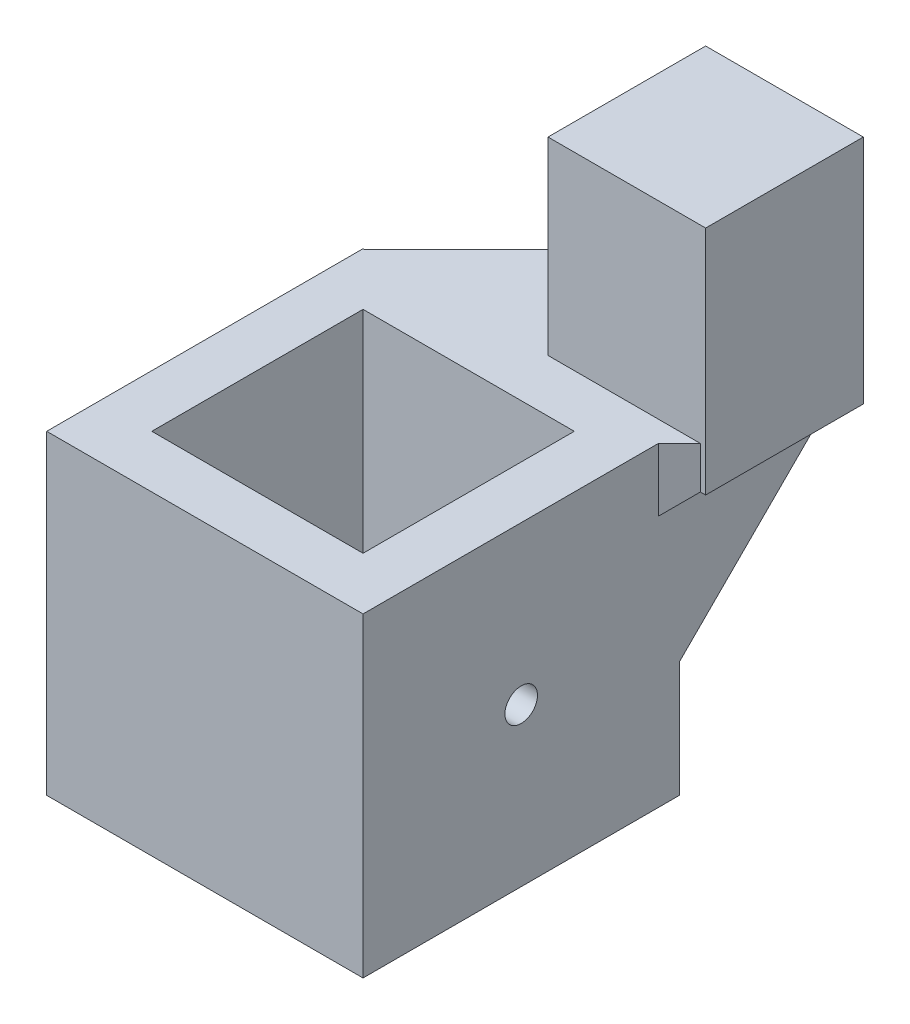
SolidWorks part; units mm, degrees
ref_plane "Front Plane" through (0, 0, 0) normal (0, 0, 1) x (1, 0, 0)
ref_plane "Top Plane" through (0, 0, 0) normal (0, 1, 0) x (1, 0, 0)
ref_plane "Right Plane" through (0, 0, 0) normal (1, 0, 0) x (0, 0, -1)
sketch "Sketch1" plane through (0, 0, 0) normal (0, 1, 0) x (1, 0, 0)
  line L0 (0, 0) -> (-20.1, 0) construction
  line L1 (0, 0) -> (80, 0)
  line L2 (0, 0) -> (0, 20.1)
  line L3 (0, 20.1) -> (80, 20.1)
  line L4 (80, 0) -> (80, 20.1)
  line L8 (-20.1, 20.1) -> (-20.1, 0)
  line L9 (-20.1, 20.1) -> (0, 0) construction
  line L10 (-20.1, 20.1) -> (0, 20.1)
  line L11 (-20.1, 20.1) -> (-20.1, 0)
  line L12 (-20.1, 0) -> (0, 0)
  line L13 (0, 20.1) -> (0, 0)
  line L14 (-20.1, 0) -> (0, 20.1) construction
  line L15 (-20.1, 0) -> (-20.1, -80)
  line L16 (0, 0) -> (0, -80)
  line L17 (-20.1, -80) -> (0, -80)
  line L18 (-20.1, 0) -> (0, 0)
  line L19 (-20.1, 20.1) -> (-100.1, 20.1)
  line L20 (-20.1, 0) -> (-100.1, 0)
  line L21 (-100.1, 20.1) -> (-100.1, 0)
  line L22 (-20.1, 20.1) -> (-20.1, 0)
  line L23 (0, 20.1) -> (0, 100.1)
  line L24 (-20.1, 20.1) -> (-20.1, 100.1)
  line L25 (0, 100.1) -> (-20.1, 100.1)
  line L26 (0, 20.1) -> (-20.1, 20.1)
  circle A5 centre (74, 14.1) radius 1.55
  circle A7 centre (74, 6) radius 1.55
  circle A9 centre (-6, -74) radius 1.55
  circle A11 centre (-14.1, -74) radius 1.55
  circle A13 centre (-94.1, 6) radius 1.55
  circle A15 centre (-94.1, 14.1) radius 1.55
  circle A17 centre (-14.1, 94.1) radius 1.55
  circle A19 centre (-6, 94.1) radius 1.55
  point P11 (-10.05, 10.05)
  point P56 (-10.05, 10.05)
  dimension "D4" = 4
  dimension "D11" = 3.1
  dimension "D13" = 3.1
  dimension "D3" = 20.1
  dimension "D5" = 80
  dimension "D24" = 6
  dimension "D25" = 6
  dimension "D26" = 6
  dimension "D27" = 6
sketch "Sketch2" plane through (0, 0, 0) normal (0, 1, 0) x (1, 0, 0)
  line L1 (-64.25, 76.68) -> (-44.25, 76.68)
  line L2 (-64.25, 76.68) -> (-64.25, 26.68)
  line L3 (-64.25, 26.68) -> (-20.1, 26.68)
  line L9 (4.25, 76.68) -> (24.25, 76.68)
  line L12 (24.25, 76.68) -> (24.25, 26.68)
  line L17 (-20.1, 26.68) -> (24.25, 26.68)
  line L18 (-54.25, 71.68) -> (14.25, 71.68) construction
  line L19 (14.25, 71.68) -> (14.25, 31.68) construction
  line L20 (-20, 71.68) -> (-20, 40) construction
  line L21 (0, 40) -> (-40, 40) construction
  line L22 (-20.1, 20.1) -> (-20.1, 0) construction
  line L23 (-64.25, 71.68) -> (-44.25, 71.68) construction
  line L25 (4.25, 71.68) -> (24.25, 71.68) construction
  line L26 (-44.25, 51.75) -> (-32.5, 40)
  line L27 (4.25, 51.75) -> (-7.5, 40)
  line L28 (4.25, 76.68) -> (4.25, 51.75)
  line L29 (-44.25, 76.68) -> (-44.25, 51.75)
  line L30 (-32.5, 40) -> (-7.5, 40)
  line L31 (-20.1, 20.1) -> (0, 20.1) construction
  circle A0 centre (-54.25, 71.68) radius 1.55
  circle A1 centre (14.25, 71.68) radius 1.55
  circle A2 centre (-54.25, 31.68) radius 1.55
  circle A3 centre (14.25, 31.68) radius 1.55
  point P4 (-20, 40)
  point P16 (14.25, 71.68)
  point P24 (-54.25, 71.68)
  point P29 (-20, 40)
  dimension "D4" = 3.1
  dimension "D5" = 3.1
  dimension "D9" = 3.1
  dimension "D13" = 3.1
  dimension "D1" = 68.5
  dimension "D2" = 20
  dimension "D3" = 5
  dimension "D6" = 31.68
  dimension "D7" = 20
  dimension "D8" = 40
  dimension "D10" = 5
  dimension "D11" = 5
  dimension "D12" = 10
  dimension "D14" = 5
  dimension "D15" = 45
  dimension "D16" = 45
  dimension "D17" = 25
sketch "Sketch3" plane through (0, 310, 0) normal (0, 1, 0) x (1, 0, 0)
  line L1 (-27.5, 62.28) -> (-12.5, 62.28)
  line L2 (-27.5, 62.28) -> (-27.5, 47.28)
  line L3 (-27.5, 47.28) -> (-12.5, 47.28)
  line L4 (-12.5, 62.28) -> (-12.5, 47.28)
  line L5 (-20, 40) -> (-20, 47.28) construction
  line L6 (0, 40) -> (-40, 40) construction
  point P5 (-20, 47.28)
  point P6 (-54.25, 71.68)
  point P14 (-27.5, 54.78)
  dimension "D1" = 16.9
  dimension "D2" = 15
  dimension "D3" = 15
sketch "Sketch4" plane through (0, 310, 0) normal (0, 1, 0) x (1, 0, 0)
  line L5 (-7.5, 40.1) -> (7.5, 40.1)
  line L6 (-7.5, 40.1) -> (-7.5, 25.1)
  line L7 (-7.5, 25.1) -> (7.5, 25.1)
  line L12 (-20.1, 20.1) -> (0, 20.1)
  line L13 (-20.1, 20.1) -> (-20.1, 0)
  line L14 (-20.1, 0) -> (0, 0)
  line L15 (0, 20.1) -> (0, 0)
  line L16 (-25.1, 25.1) -> (5, 25.1)
  line L17 (-25.1, 25.1) -> (-25.1, -5)
  line L18 (-25.1, -5) -> (5, -5)
  line L19 (5, 25.1) -> (5, -5)
  line L26 (7.5, 40.1) -> (7.5, 25.1)
  point P4 (0, 25.1)
  dimension "D1" = 5
  dimension "D2" = 5
  dimension "D3" = 5
  dimension "D4" = 5
  dimension "D5" = 0
  dimension "D6" = 15
  dimension "D7" = 15
extrude "Boss-Extrude6" add sketch "Sketch4" against normal blind 5 contours L19 L16 L17 L18 region at (-1.25, 310, -24.6743)
extrude "Boss-Extrude7" add sketch "Sketch4<4>" against normal blind 15 and the other way blind 15 contours L19 L16 L17 L18 L12 L15 L14 L13 region at (-1.25, 310, -24.6743)
sketch "Sketch4<4>" plane through (0, 310, 0) normal (0, 1, 0) x (1, 0, 0) same geometry as "Sketch4"
sketch "Sketch5" plane through (5, 0, 0) normal (1, 0, 0) x (0, 0, -1)
  line L0 (-5, 325) -> (25.1, 295) construction
  circle A0 centre (10.05, 310) radius 1.55
  point P6 (23.3607, 295.767)
  point P8 (0, 0)
  point P9 (-3.5123, 324.3169)
  dimension "D1" = 3.1
extrude "Cut-Extrude1" cut sketch "Sketch5" against normal blind 54
extrude "Boss-Extrude8" add sketch "Sketch4<5>" along normal blind 18 from offset 15 separate body contours L26 L5 L6 L7 region at (0, 310, -32.6)
sketch "Sketch4<5>" plane through (0, 310, 0) normal (0, 1, 0) x (1, 0, 0) same geometry as "Sketch4"
sketch "Sketch6" plane through (0, 325, 0) normal (0, 1, 0) x (1, 0, 0)
  line L7 (7.5, 40.1) -> (-10, 40.1)
  line L8 (7.5, 40.1) -> (7.5, 25.1)
  line L9 (7.5, 25.1) -> (-10, 25.1)
  line L10 (-10, 40.1) -> (-10, 25.1)
  line L12 (-7.5, 40.1) -> (-7.5, 25.1) construction
  line L13 (-25.1, 25.1) -> (5, 25.1) construction
  point P7 (0, 0)
  point P8 (0, 0)
  point P9 (0, 0)
  dimension "D1" = 2.5
extrude "Boss-Extrude9" add sketch "Sketch6" against normal blind 4
chamfer "Chamfer1" distance 15 angle 45 1 edges at (-2.5, 321, -25.1)
chamfer "Chamfer2" distance 15 angle 45 1 edges at (-10, 315.5, -25.1)
chamfer "Chamfer3" distance 2 angle 45 2 edges at (5, 323, -25.1) (5, 321, -32.6)
